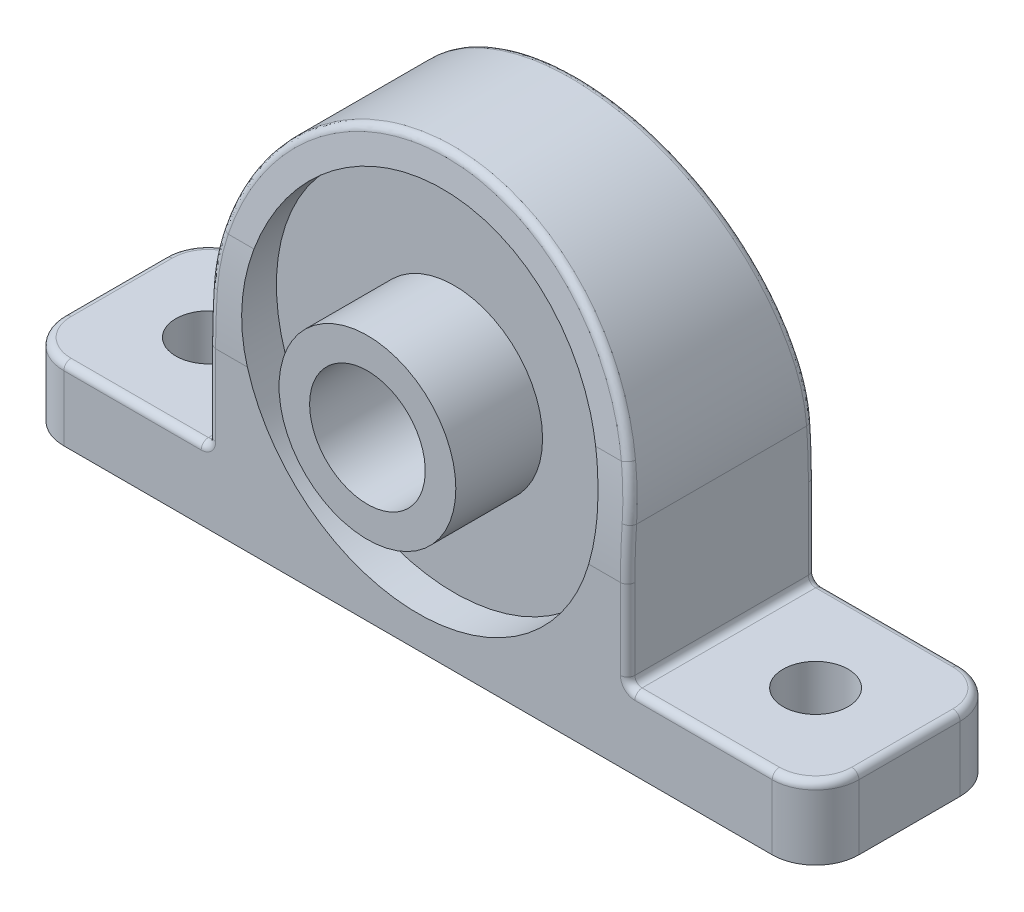
SolidWorks part; units mm, degrees
ref_plane "Plan de face" through (0, 0, 0) normal (0, 0, 1) x (1, 0, 0)
ref_plane "Plan de dessus" through (0, 0, 0) normal (0, 1, 0) x (1, 0, 0)
ref_plane "Plan de droite" through (0, 0, 0) normal (1, 0, 0) x (0, 0, -1)
sketch "Esquisse1" plane through (0, 0, 0) normal (0, 0, 1) x (1, 0, 0)
  line L0 (13, 14.5) -> (13, 5)
  line L1 (55, 29) -> (0, 29) construction
  line L2 (55, 29) -> (55, 0) construction
  line L3 (55, 0) -> (0, 0) construction
  line L4 (0, 29) -> (0, 0) construction
  line L5 (55, 29) -> (0, 0) construction
  line L6 (55, 0) -> (55, 5)
  line L7 (0, 5) -> (55, 5) construction
  line L8 (13, 5) -> (0, 5)
  line L9 (0, 5) -> (0, 0)
  line L10 (55, 0) -> (0, 0)
  line L11 (55, 5) -> (42, 5)
  line L12 (42, 5) -> (42, 14.5)
  circle A0 centre (27.5, 14.5) radius 4
  circle A1 centre (27.5, 14.5) radius 14.5 construction
  arc A2 (13, 14.5) -> (42, 14.5) centre (27.5, 14.5) cw
  point P0 (27.5, 14.5)
  dimension "D4" = 8
  dimension "D1" = 55
  dimension "D2" = 29
  dimension "D5" = 5
extrude "Boss.-Extru.1" add sketch "Esquisse1" along normal blind 13
sketch "Esquisse2" plane through (0, 0, 13) normal (0, 0, 1) x (1, 0, 0)
  circle A0 centre (27.5, 14.5) radius 12.2968
extrude "Enlèv. mat.-Extru.1" cut sketch "Esquisse2" against normal blind 2.5
sketch "Esquisse3" plane through (0, 0, 0) normal (0, 0, -1) x (-1, 0, 0)
  circle A0 centre (-27.5, 14.5) radius 12.2968
  circle A1 centre (-27.5, 14.5) radius 12.2968 construction
extrude "Enlèv. mat.-Extru.2" cut sketch "Esquisse3" against normal blind 2.5
sketch "Esquisse4" plane through (0, 0, 0) normal (0, -1, 0) x (1, 0, 0)
  line L0 (0, 6.5) -> (6.5, 6.5) construction
  line L3 (0, 13) -> (0, 0) construction
  line L4 (6.5, 6.5) -> (48.5, 6.5) construction
  line L5 (48.5, 6.5) -> (55, 6.5) construction
  line L6 (55, 13) -> (55, 0) construction
  circle A0 centre (6.5, 6.5) radius 2.25
  circle A1 centre (48.5, 6.5) radius 2.25
  dimension "D1" = 4.5
  dimension "D2" = 42
extrude "Enlèv. mat.-Extru.3" cut sketch "Esquisse4" against normal through all
sketch "Esquisse5" plane through (0, 0, 0) normal (-1, 0, 0) x (0, 0, 1)
  line L0 (0, 14.5) -> (2, 29)
  line L1 (13, 29) -> (0, 29) construction
  line L2 (2, 29) -> (11, 29)
  line L3 (11, 29) -> (13, 14.5)
  line L4 (13, 14.5) -> (15.7973, 14.5)
  line L5 (15.7973, 14.5) -> (15.7973, 29.9685)
  line L6 (15.7973, 29.9685) -> (-2.6826, 29.9685)
  line L7 (-2.6826, 29.9685) -> (-2.6826, 14.5)
  line L8 (-2.6826, 14.5) -> (0, 14.5)
  line L9 (0, 29) -> (0, 14.5) construction
  dimension "D1" = 2
extrude "Enlèv. mat.-Extru.4" cut sketch "Esquisse5" against normal through all
sketch "Esquisse6" plane through (0, 0, 10.5) normal (0, 0, 1) x (1, 0, 0)
  circle A0 centre (27.5, 14.5) radius 4
  circle A1 centre (27.5, 14.5) radius 6.1146
  circle A2 centre (27.5, 14.5) radius 4 construction
extrude "Boss.-Extru.2" add sketch "Esquisse6" along normal blind 6
sketch "Esquisse7" plane through (0, 0, 2.5) normal (0, 0, -1) x (-1, 0, 0)
  circle A0 centre (-27.5, 14.5) radius 4
  circle A1 centre (-27.5, 14.5) radius 6.1146
  circle A2 centre (-27.5, 14.5) radius 4 construction
  circle A3 centre (-27.5, 14.5) radius 6.1146 construction
extrude "Boss.-Extru.3" add sketch "Esquisse7" along normal blind 0.5
fillet "Congé1" radius 50 4 edges at (40.8984, 14.5, 13) (14.1016, 14.5, 13) (40.8984, 14.5, 0) (14.1016, 14.5, 0)
fillet "Congé2" radius 3 4 edges at (55, 2.5, 0) (55, 2.5, 13) (0, 2.5, 13) (0, 2.5, 0)
fillet "Congé3" radius 0.5 26 edges at (0, 5, 6.5) (55, 5, 6.5) (54.1213, 5, 0.8787) (0.8787, 5, 0.8787) (0.8787, 5, 12.1213) (54.1213, 5, 12.1213) (47, 5, 0) (8, 5, 0) (8, 5, 13) (47, 5, 13) (42, 8.034, 0) (42, 12.785, 0.0295) (13, 8.034, 0) (13, 12.785, 0.0295) (13, 8.034, 13) (13, 12.785, 12.9705) (42, 8.034, 13) (42, 12.785, 12.9705) (13, 5, 6.5) (42, 5, 6.5) (27.5, 29, 2) (27.5, 29, 11)
sketch "Croquis2" plane through (0, 0, 0) normal (0, -1, 0) x (1, 0, 0)
  line L0 (27.5, 16.5) -> (27.5, 0) construction
  line L1 (33.6146, 16.5) -> (21.3854, 16.5) construction
  line L2 (3, 0) -> (52, 0) construction
  line L3 (27.5, 0) -> (-13.2591, 0) construction
  line L4 (0, 10) -> (0, 0) construction
